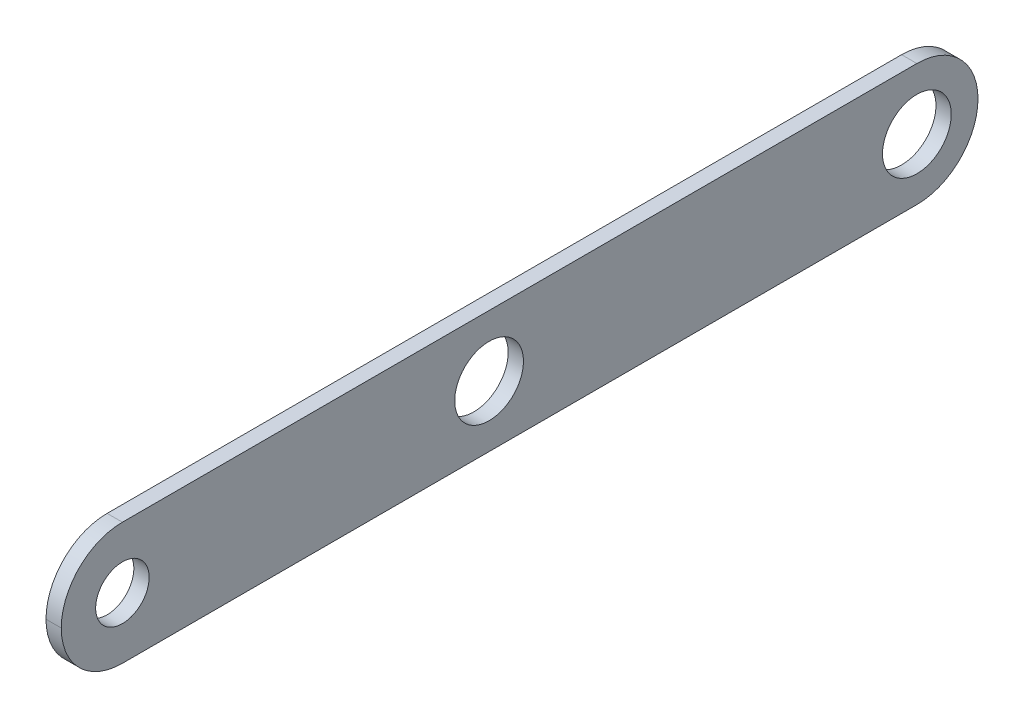
SolidWorks part; units mm, degrees
ref_plane "Front Plane" through (0, 0, 0) normal (0, 0, 1) x (1, 0, 0)
ref_plane "Top Plane" through (0, 0, 0) normal (0, 1, 0) x (1, 0, 0)
ref_plane "Right Plane" through (0, 0, 0) normal (1, 0, 0) x (0, 0, -1)
sketch "Sketch1" plane through (0, 0, 0) normal (1, 0, 0) x (0, 0, -1)
  line L1 (0, 0) -> (381, 0)
  line L2 (0, 0) -> (0, 50.8)
  line L3 (0, 50.8) -> (381, 50.8)
  line L4 (381, 0) -> (381, 50.8)
  circle A0 centre (25.4, 25.4) radius 11.1125
  circle A1 centre (355.6, 25.4) radius 14.2875
  circle A2 centre (177.8, 25.4) radius 14.2875
  dimension "D3" = 22.225
  dimension "D6" = 28.575
  dimension "D1" = 381
  dimension "D2" = 50.8
  dimension "D4" = 25.4
  dimension "D5" = 25.4
  dimension "D7" = 152.4
  dimension "D8" = 25.4
extrude "Boss-Extrude1" add sketch "Sketch1" along normal blind 6.35
fillet "Fillet3" radius 25.4 4 edges at (3.175, 0, 0) (3.175, 50.8, 0) (3.175, 0, -381) (3.175, 50.8, -381)
